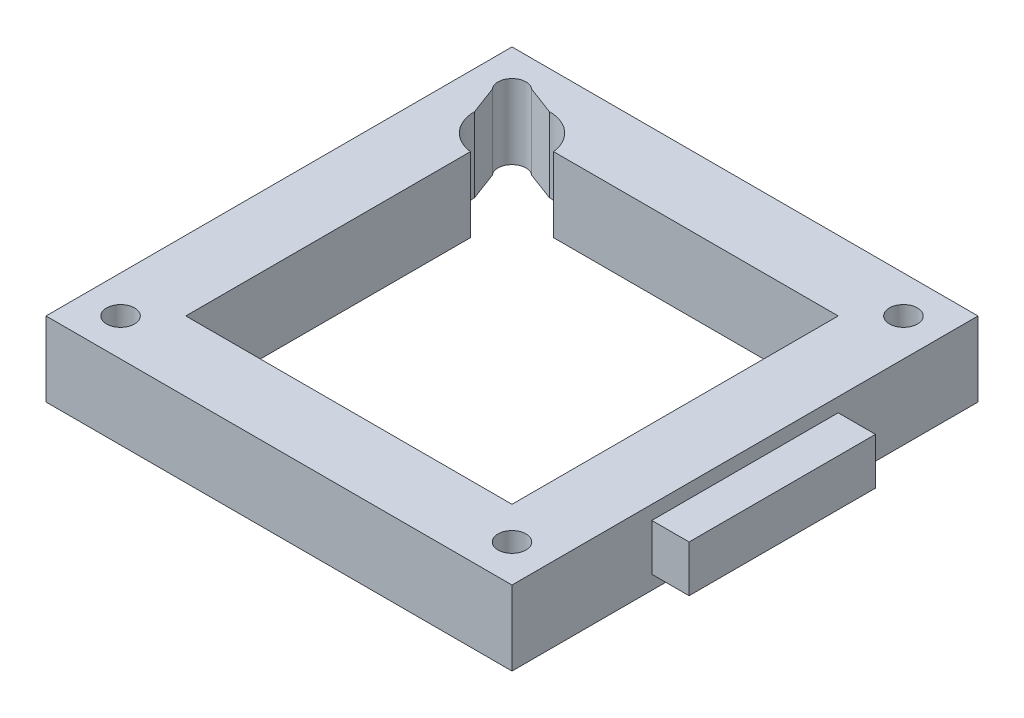
SolidWorks part; units mm, degrees
ref_plane "Front Plane" through (0, 0, 0) normal (0, 0, 1) x (1, 0, 0)
ref_plane "Top Plane" through (0, 0, 0) normal (0, 1, 0) x (1, 0, 0)
ref_plane "Right Plane" through (0, 0, 0) normal (1, 0, 0) x (0, 0, -1)
sketch "Sketch1" plane through (0, 0, 0) normal (0, 1, 0) x (1, 0, 0)
  line L0 (17.5, 17.5) -> (-13.0314, 17.5)
  line L1 (-25, -25) -> (25, -25)
  line L2 (-25, -25) -> (-25, 25)
  line L3 (-25, 25) -> (25, 25)
  line L4 (25, -25) -> (25, 25)
  line L5 (0, 25) -> (0, -25) construction
  line L6 (-25, 0) -> (25, 0) construction
  line L11 (0, 20) -> (0, -20) construction
  line L12 (-20, 0) -> (20, 0) construction
  line L13 (-17.5, -17.5) -> (17.5, -17.5)
  line L16 (17.5, -17.5) -> (17.5, 17.5)
  line L17 (0, 17.5) -> (0, -17.5) construction
  line L18 (-17.5, 0) -> (17.5, 0) construction
  line L19 (-17.5, -17.5) -> (-17.5, 13.0314)
  line L20 (-22.1301, 20.0137) -> (-21, 17)
  line L21 (-20.0137, 22.1301) -> (-17, 21)
  arc A0 (-20.0137, 22.1301) -> (-22.1301, 20.0137) centre (-21, 21) ccw
  circle A1 centre (21, 21) radius 1.5
  circle A2 centre (21, -21) radius 1.5
  circle A3 centre (-21, -21) radius 1.5
  arc A4 (-21, 17) -> (-17, 21) centre (-17, 17) ccw
  point P0 (0, 0)
  point P4 (0, 0)
  point P13 (0, 0)
  dimension "D1" = 50
  dimension "D2" = 50
  dimension "D4" = 35
extrude "Support" add sketch "Sketch1" along normal blind 8 contours L1 L4 L3 L2 A4 L0 L16 L13 L19 L20 A0 L21 A1 A2 A3 region at (-24.2929, 0, 0)
sketch "Sketch2" plane through (0, 0, 0) normal (0, 0, 1) x (1, 0, 0)
  line L4 (-10, 1.5) -> (10, 1.5)
  line L5 (-10, 1.5) -> (-10, 6.5)
  line L6 (-10, 6.5) -> (10, 6.5)
  line L7 (10, 1.5) -> (10, 6.5)
  line L8 (0, 6.5) -> (0, 1.5) construction
  line L9 (-10, 4) -> (10, 4) construction
  point P6 (0, 4)
  dimension "D1" = 20
  dimension "D2" = 5
sketch "Sketch3" plane through (0, 0, 0) normal (1, 0, 0) x (0, 0, -1)
  line L4 (-10, 1.5) -> (10, 1.5)
  line L5 (-10, 1.5) -> (-10, 6.5)
  line L6 (-10, 6.5) -> (10, 6.5)
  line L7 (10, 1.5) -> (10, 6.5)
  line L8 (0, 6.5) -> (0, 1.5) construction
  line L9 (-10, 4) -> (10, 4) construction
  point P6 (0, 4)
  dimension "D1" = 20
  dimension "D2" = 5
extrude "North Cut" cut sketch "Sketch2" along normal blind 4 from surface starting at face at (0, 4, -25)
extrude "West Cut" cut sketch "Sketch3" along normal blind 4 from surface starting at face at (-25, 4, 0)
extrude "East Dowel" add sketch "Sketch3<3>" along normal blind 4 from surface starting at face at (25, 4, 0)
sketch "Sketch3<3>" plane through (0, 0, 0) normal (1, 0, 0) x (0, 0, -1) same geometry as "Sketch3"
